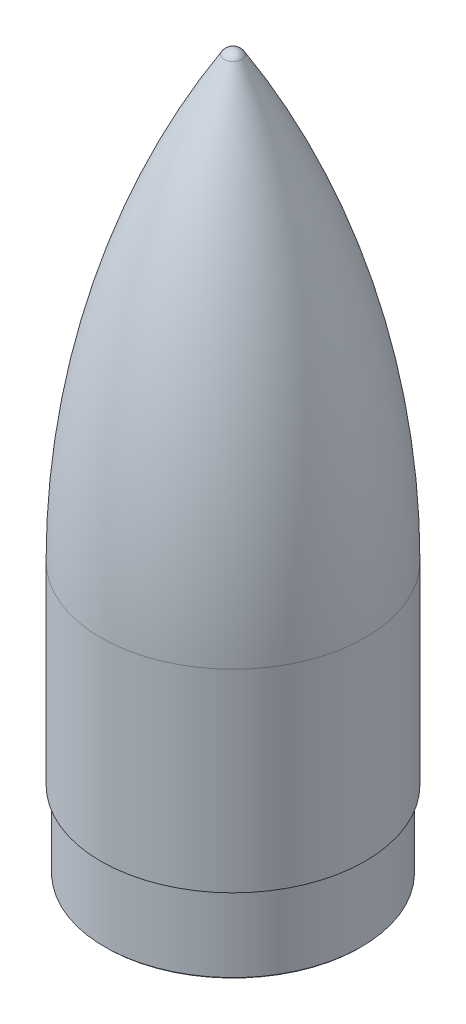
SolidWorks part; units mm, degrees
material "PBT Общее назначение"
ref_plane "Спереди" through (0, 0, 0) normal (0, 0, 1) x (1, 0, 0)
ref_plane "Сверху" through (0, 0, 0) normal (0, 1, 0) x (1, 0, 0)
ref_plane "Справа" through (0, 0, 0) normal (1, 0, 0) x (0, 0, -1)
sketch "Эскиз1" plane through (0, 0, 0) normal (0, 0, 1) x (1, 0, 0)
  line L0 (0, 0) -> (0, 54.4254) construction
  line L1 (49.7, 0) -> (30.5, 0)
  line L2 (26.5, 167) -> (30.5, 155)
  line L3 (49.7, 0) -> (49.7, 30)
  line L4 (49.7, 30) -> (51.2, 30)
  line L5 (51.2, 30) -> (51.2, 105)
  line L6 (30.5, 155) -> (30.5, 0)
  line L7 (0, 167) -> (26.5, 167)
  line L8 (0, 277) -> (0, 167)
  arc A0 (51.2, 105) -> (3.4147, 275.0832) centre (-275.3831, 105) ccw
  arc A1 (0, 277) -> (3.4147, 275.0832) centre (0, 273) cw
  point P11 (39.0268, 193.3342)
  dimension "D9" = 326.5831
  dimension "D6" = 4
  dimension "D1" = 51.2
  dimension "D2" = 1.5
  dimension "D3" = 110
  dimension "D4" = 30
  dimension "D5" = 75
  dimension "D7" = 155
  dimension "D8" = 12
  dimension "D10" = 19.2
  dimension "D11" = 4
  dimension "D12" = 30.5
  dimension "D13" = 20.2116
  dimension "D14" = 277
  dimension "D15" = 51.2
  dimension "D16" = 49.7
revolve "Основа" add sketch "Эскиз1" angle 360 about L0
shell "Оболочка1" thickness 3 removed face at (0, 155, -30.5) removed face at (0, 167, -26.5) removed face at (0, 0, -49.7) removed face at (0, 0, -30.5)
fillet "Скругление внутри" radius 3 1 edges at (0, 33, -48.2)
chamfer "Фаска внизу" distance 0.5 angle 45 1 edges at (0, 0, -49.7)
sketch "Эскиз3" plane through (0, 0, 0) normal (1, 0, 0) x (0, 0, -1)
  line L0 (0, 0) -> (49.2, 0) construction
  line L1 (-49.2, 0) -> (49.2, 0) construction
  line L2 (48, 10) -> (48, 8)
  line L3 (48, 2) -> (48, 0)
  line L4 (48, 5) -> (48, 0) construction
  arc A0 (48, 10) -> (48, 0) centre (48, 5) ccw
  arc A1 (48, 8) -> (48, 2) centre (48, 5) ccw
  dimension "D2" = 3
  dimension "D3" = 5
  dimension "D1" = 49.2
  dimension "D4" = 48
extrude "Петля крепления" [suppressed] add sketch "Эскиз3" along normal mid plane 5
sketch "Эскиз4" plane through (0, 0, 0) normal (1, 0, 0) x (0, 0, -1)
  line L0 (0, 0) -> (0, 54) construction
  line L1 (-1.7321, 51) -> (0, 54)
  line L2 (1.7321, 51) -> (0, 54)
  arc A0 (1.7321, 51) -> (-1.7321, 51) centre (0, 50) cw
  dimension "D1" = 2
  dimension "D2" = 3
  dimension "D3" = 60
  dimension "D4" = 50
extrude "Вырез для выравнивания давления" cut sketch "Эскиз4" against normal up to surface (51.1707 mm away) up to face at (0, 105, -51.2)
